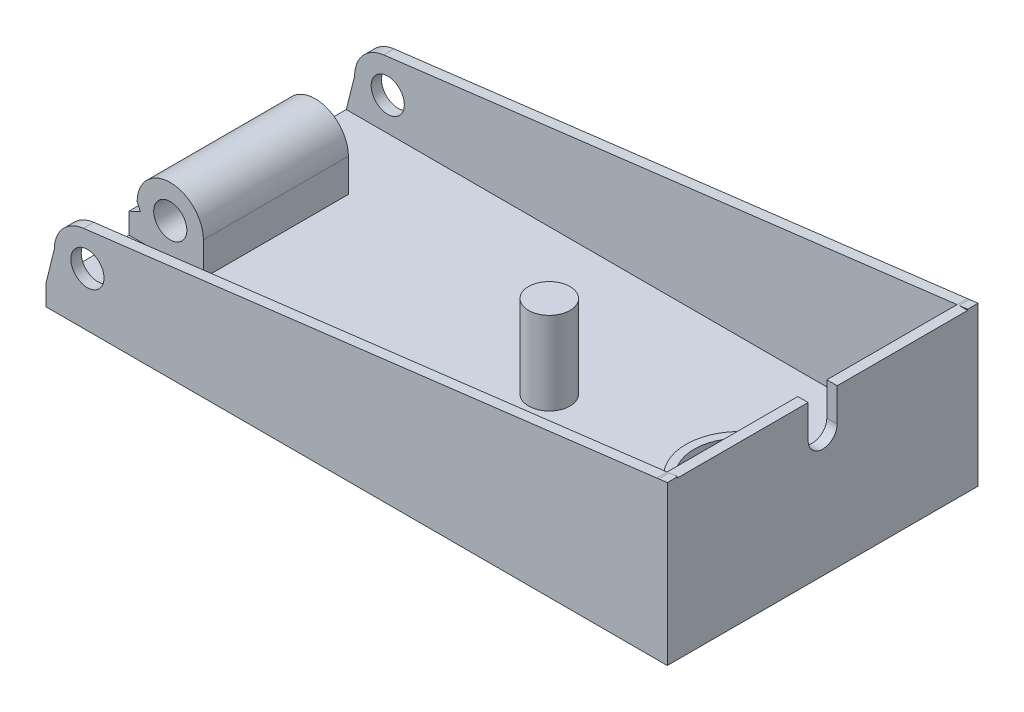
SolidWorks part; units mm, degrees
ref_plane "Front Plane" through (0, 0, 0) normal (0, 0, 1) x (1, 0, 0)
ref_plane "Top Plane" through (0, 0, 0) normal (0, 1, 0) x (1, 0, 0)
ref_plane "Right Plane" through (0, 0, 0) normal (1, 0, 0) x (0, 0, -1)
sketch "Sketch2" plane through (0, 0, 0) normal (0, 1, 0) x (1, 0, 0)
  line L1 (-75, 37.5) -> (75, 37.5)
  line L2 (-75, 37.5) -> (-75, -37.5)
  line L3 (-75, -37.5) -> (75, -37.5)
  line L4 (75, 37.5) -> (75, -37.5)
  line L5 (-75, 37.5) -> (75, -37.5) construction
  line L6 (-75, -37.5) -> (75, 37.5) construction
  point P0 (0, 0)
  dimension "D1" = 75
  dimension "D2" = 150
extrude "Boss-Extrude1" add sketch "Sketch2" along normal mid plane 5
sketch "Sketch3" plane through (0, 0, 0) normal (0, 0, 1) x (1, 0, 0)
  line L1 (-75, 2.5) -> (75, 2.5) construction
  line L2 (-57, 10.5) -> (-57, 2.5)
  line L3 (-75, 2.5) -> (-57, 2.5)
  line L4 (-65, 23.813) -> (-65, -18.0629) construction
  line L5 (-75, 2.5) -> (-75, 7.5)
  line L6 (-75, 10.5) -> (-73, 10.5) construction
  line L7 (-75, 8) -> (-73, 8) construction
  line L8 (-73, 8) -> (-73, 10.5) construction
  line L9 (-75, 8) -> (-75, 10.5) construction
  line L11 (-75, 7.5) -> (-75, 8) construction
  line L12 (-73, 10.5) -> (-72.2081, 8.8019)
  line L13 (-75, 7.5) -> (-72.2081, 8.8019)
  arc A0 (-73, 10.5) -> (-57, 10.5) centre (-65, 10.5) cw
  circle A1 centre (-65, 10.5) radius 4
  dimension "D1" = 8
  dimension "D2" = 8
  dimension "D3" = 8
  dimension "D4" = 65
  dimension "D5" = 2
  dimension "D6" = 5.5
  dimension "D7" = 0.5
  dimension "D8" = 90
  dimension "D9" = 115
extrude "Boss-Extrude2" add sketch "Sketch3" along normal mid plane 35
sketch "Sketch4" plane through (0, 2.5, 0) normal (0, 1, 0) x (1, 0, 0)
  circle A0 centre (9, 0) radius 5
  dimension "D1" = 10
  dimension "D2" = 9
extrude "Boss-Extrude3" add sketch "Sketch4" along normal blind 20
sketch "Sketch7" plane through (0, 2.5, 0) normal (0, 1, 0) x (1, 0, 0)
  circle A2 centre (55, 0) radius 11
  circle A3 centre (55, 0) radius 13
  dimension "D1" = 22
  dimension "D2" = 26
  dimension "D3" = 55
extrude "Boss-Extrude4" add sketch "Sketch7" along normal blind 6
sketch "Sketch9" plane through (0, 0, 0) normal (0, 0, 1) x (1, 0, 0)
  line L0 (-75, 2.5) -> (75, 35.7542) construction
  line L1 (75, -6.0645) -> (75, 36.8852) construction
  line L2 (-75, 2.5) -> (75, 2.5) construction
  line L3 (75, 35.7542) -> (75, 2.5)
  line L4 (75, 2.5) -> (-75, 2.5)
  line L5 (75, 35.7542) -> (-65.9752, 18.4403)
  line L6 (-75, 17.332) -> (-75, 2.5) construction
  line L7 (-75, 2.5) -> (-75, -2.5) construction
  line L8 (-73, 10.5) -> (-75, 2.5)
  line L11 (-65.9752, 18.4403) -> (-75, 17.332) construction
  arc A0 (-57, 10.5) -> (-73, 10.5) centre (-65, 10.5) ccw construction
  arc A1 (-65.9752, 18.4403) -> (-73, 10.5) centre (-65, 10.5) ccw
  arc A2 (-65, 18.5) -> (-65.9752, 18.4403) centre (-65, 10.5) ccw construction
  point P14 (-65, 18.5)
  dimension "D2" = 8
  dimension "D1" = 12.5
extrude "Boss-Extrude5" add sketch "Sketch9" against normal blind 2.5 from surface starting at face at (0, 0, 37.5)
extrude "Boss-Extrude6" add sketch "Sketch9<2>" along normal blind 2.5 from surface starting at face at (0, 0, -37.5)
sketch "Sketch9<2>" plane through (0, 0, 0) normal (0, 0, 1) x (1, 0, 0) same geometry as "Sketch9"
sketch "Sketch10" plane through (75, 0, 0) normal (1, 0, 0) x (0, 0, -1)
  line L1 (37.5, 35.5) -> (37.5, -2.5)
  line L2 (37.5, -2.5) -> (-37.5, -2.5)
  line L3 (-37.5, -2.5) -> (-37.5, 35.5)
  line L4 (37.5, 35.7542) -> (37.5, -2.5) construction
  line L5 (-37.5, 35.7542) -> (-37.5, -2.5) construction
  line L6 (-37.5, 35.5) -> (-3.5, 35.5)
  line L7 (0, 47.3912) -> (0, -19.7103) construction
  line L8 (-3.5, 35.5) -> (-3.5, 27.5)
  line L9 (3.5, 35.5) -> (3.5, 27.5)
  line L10 (-3.5, 35.5) -> (0, 35.5) construction
  line L11 (3.5, 35.5) -> (37.5, 35.5)
  line L12 (0, 35.5) -> (3.5, 35.5) construction
  arc A0 (-3.5, 27.5) -> (3.5, 27.5) centre (0, 27.5) ccw
  point P19 (0, 27.2484)
  dimension "D2" = 3.5
  dimension "D3" = 3.5
  dimension "D1" = 38
  dimension "D4" = 8
extrude "Boss-Extrude7" add sketch "Sketch10" against normal blind 2.5
sketch "Sketch11" plane through (0, -2.5, 0) normal (0, -1, 0) x (1, 0, 0)
  line L0 (-53.5, 32.5) -> (-53.5, -32.5)
  line L1 (-63.5, 32.5) -> (-66.5, 32.5)
  line L2 (-63.5, 32.5) -> (-63.5, -32.5)
  line L3 (-63.5, -32.5) -> (-66.5, -32.5)
  line L4 (-66.5, 32.5) -> (-66.5, -32.5)
  line L5 (-63.5, 32.5) -> (-66.5, -32.5) construction
  line L6 (-63.5, -32.5) -> (-66.5, 32.5) construction
  line L7 (-53.5, 32.5) -> (-56.5, 32.5)
  line L8 (-56.5, 32.5) -> (-56.5, -32.5)
  line L9 (-53.5, -32.5) -> (-56.5, -32.5)
  line L10 (-43.5, 32.5) -> (-43.5, -32.5)
  line L11 (-43.5, 32.5) -> (-46.5, 32.5)
  line L12 (-46.5, 32.5) -> (-46.5, -32.5)
  line L13 (-43.5, -32.5) -> (-46.5, -32.5)
  line L14 (-33.5, 32.5) -> (-33.5, -32.5)
  line L15 (-33.5, 32.5) -> (-36.5, 32.5)
  line L16 (-36.5, 32.5) -> (-36.5, -32.5)
  line L17 (-33.5, -32.5) -> (-36.5, -32.5)
  line L18 (-23.5, 32.5) -> (-23.5, -32.5)
  line L19 (-23.5, 32.5) -> (-26.5, 32.5)
  line L20 (-26.5, 32.5) -> (-26.5, -32.5)
  line L21 (-23.5, -32.5) -> (-26.5, -32.5)
  line L22 (-13.5, 32.5) -> (-13.5, -32.5)
  line L23 (-13.5, 32.5) -> (-16.5, 32.5)
  line L24 (-16.5, 32.5) -> (-16.5, -32.5)
  line L25 (-13.5, -32.5) -> (-16.5, -32.5)
  line L26 (-3.5, 32.5) -> (-3.5, -32.5)
  line L27 (-3.5, 32.5) -> (-6.5, 32.5)
  line L28 (-6.5, 32.5) -> (-6.5, -32.5)
  line L29 (-3.5, -32.5) -> (-6.5, -32.5)
  line L30 (6.5, 32.5) -> (6.5, -32.5)
  line L31 (6.5, 32.5) -> (3.5, 32.5)
  line L32 (3.5, 32.5) -> (3.5, -32.5)
  line L33 (6.5, -32.5) -> (3.5, -32.5)
  line L34 (16.5, 32.5) -> (16.5, -32.5)
  line L35 (16.5, 32.5) -> (13.5, 32.5)
  line L36 (13.5, 32.5) -> (13.5, -32.5)
  line L37 (16.5, -32.5) -> (13.5, -32.5)
  line L38 (26.5, 32.5) -> (26.5, -32.5)
  line L39 (26.5, 32.5) -> (23.5, 32.5)
  line L40 (23.5, 32.5) -> (23.5, -32.5)
  line L41 (26.5, -32.5) -> (23.5, -32.5)
  line L42 (36.5, 32.5) -> (36.5, -32.5)
  line L43 (36.5, 32.5) -> (33.5, 32.5)
  line L44 (33.5, 32.5) -> (33.5, -32.5)
  line L45 (36.5, -32.5) -> (33.5, -32.5)
  line L46 (46.5, 32.5) -> (46.5, -32.5)
  line L47 (46.5, 32.5) -> (43.5, 32.5)
  line L48 (43.5, 32.5) -> (43.5, -32.5)
  line L49 (46.5, -32.5) -> (43.5, -32.5)
  line L50 (56.5, 32.5) -> (56.5, -32.5)
  line L51 (56.5, 32.5) -> (53.5, 32.5)
  line L52 (53.5, 32.5) -> (53.5, -32.5)
  line L53 (56.5, -32.5) -> (53.5, -32.5)
  line L54 (66.5, 32.5) -> (66.5, -32.5)
  line L55 (66.5, 32.5) -> (63.5, 32.5)
  line L56 (63.5, 32.5) -> (63.5, -32.5)
  line L57 (66.5, -32.5) -> (63.5, -32.5)
  point P0 (-65, 0)
  dimension "D1" = 3
  dimension "D2" = 65
  dimension "D3" = 65
  dimension "D4" = 14
extrude "Boss-Extrude8" add sketch "Sketch11" along normal blind 1 contours L13 L10 L11 L12 | L17 L14 L15 L16 | L21 L18 L19 L20 | L25 L22 L23 L24 | L29 L26 L27 L28 | L33 L30 L31 L32 | L37 L34 L35 L36 | L41 L38 L39 L40 | L45 L42 L43 L44 | L49 L46 L47 L48 | L53 L50 L51 L52 | L57 L54 L55 L56 | L2 L1 L4 L3 | L0 L9 L8 L7 region at (-45, -2.5, 0) region at (-35, -2.5, 0) region at (-25, -2.5, 0) region at (-15, -2.5, 0) region at (-5, -2.5, 0) region at (5, -2.5, 0) region at (15, -2.5, 0) region at (25, -2.5, 0) region at (35, -2.5, 0) region at (45, -2.5, 0) region at (55, -2.5, 0) region at (65, -2.5, 0)
sketch "Sketch12" plane through (0, 0, -37.5) normal (0, 0, -1) x (-1, 0, 0)
  circle A0 centre (65, 10.5) radius 4
extrude "Cut-Extrude1" cut sketch "Sketch12" against normal through all both and the other way through all
